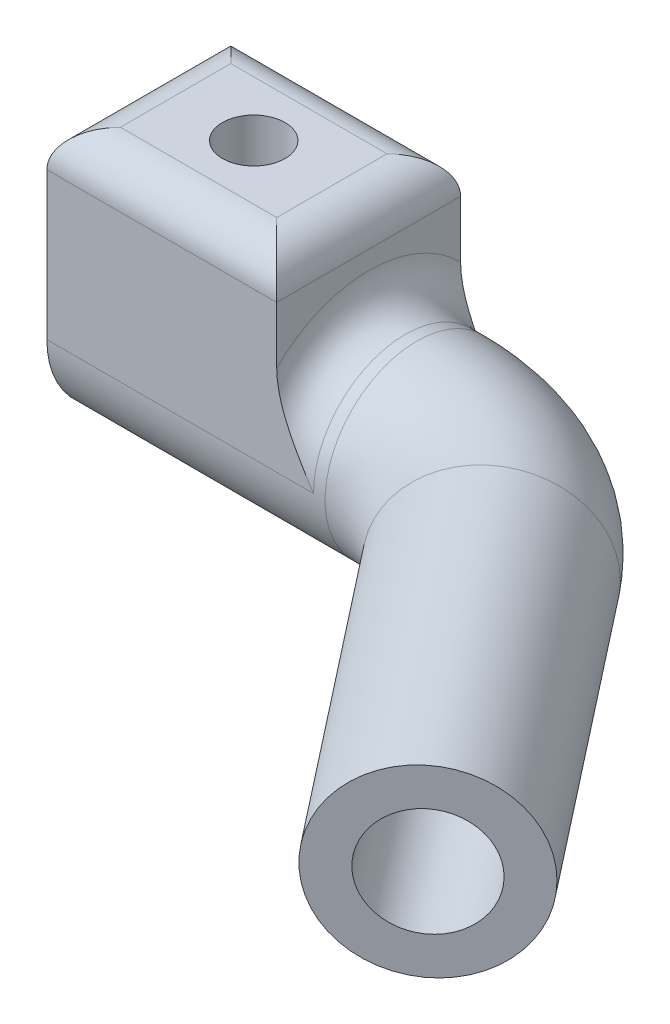
SolidWorks part; units mm, degrees
ref_plane "Front" through (0, 0, 0) normal (0, 0, 1) x (1, 0, 0)
ref_plane "Top" through (0, 0, 0) normal (0, 1, 0) x (1, 0, 0)
ref_plane "Right" through (0, 0, 0) normal (1, 0, 0) x (0, 0, -1)
sketch "Sketch1" plane through (0, 0, 0) normal (0, 1, 0) x (1, 0, 0)
  line L0 (0, 0) -> (15.1284, 0)
  line L1 (23.0028, -3.8361) -> (35.4097, -19.6861)
  line L2 (15.1284, 0) -> (20, 0) construction
  line L3 (23.0028, -3.8361) -> (20, 0) construction
  arc A0 (23.0028, -3.8361) -> (15.1284, 0) centre (15.1284, -10) ccw
  point P10 (20, 0)
  dimension "D1" = 10
  dimension "D2" = 128.053
  dimension "D3" = 20
  dimension "D4" = 25
sketch "Sketch2" plane through (0, 0, 0) normal (1, 0, 0) x (0, 0, -1)
  circle A1 centre (0, 0) radius 5
  dimension "D1" = 10
sweep "Sweep1" add profiles "Sketch2" path "Sketch1"
sketch "Sketch3" plane through (0, 0, 0) normal (0, 1, 0) x (1, 0, 0)
  line L1 (0, 0) -> (6.25, 0) construction
  line L2 (0, -5) -> (15.1284, -5) construction
  line L3 (12.5, 5) -> (0, 5)
  line L4 (12.5, 5) -> (12.5, -5)
  line L5 (12.5, -5) -> (0, -5)
  line L6 (0, 5) -> (0, -5)
  line L7 (12.5, 5) -> (0, -5) construction
  line L8 (12.5, -5) -> (0, 5) construction
  line L9 (0, 5) -> (0, -5) construction
  dimension "D1" = 12.5
extrude "Boss-Extrude1" add sketch "Sketch3" along normal blind 10
sketch "Sketch4" plane through (0, 0, 0) normal (-1, 0, 0) x (0, 0, 1)
  line L0 (-2.6268, 1.55) -> (2.6268, 1.55)
  circle A0 centre (0, 0) radius 3.05 construction
  arc A1 (-2.6268, 1.55) -> (2.6268, 1.55) centre (0, 0) ccw
  point P5 (0, -3.05)
  dimension "D1" = 6.1
  dimension "D2" = 4.6
extrude "Cut-Extrude1" cut sketch "Sketch4" against normal blind 12.5
sketch "Sketch5" plane through (23.0084, 0, 29.3935) normal (0.6164, 0, 0.7874) x (0.7874, 0, -0.6164)
  line L0 (3.0819, 10) -> (-3.0819, 10) construction
  circle A0 centre (15.7489, 0) radius 2.95
  dimension "D1" = 5.9
sketch "Sketch6" plane through (0, 10, 0) normal (0, 1, 0) x (1, 0, 0)
  line L0 (0, 5) -> (12.5, -5) construction
  line L1 (0, -5) -> (12.5, 5) construction
  circle A0 centre (6.25, 0) radius 1.7
  point P8 (6.25, 0)
  dimension "D1" = 3.4
extrude "Cut-Extrude2" cut sketch "Sketch6" against normal up to next
extrude "Cut-Extrude3" cut sketch "Sketch5" against normal blind 10
fillet "Fillet1" radius 2 5 edges at (12.5, 5, 0) (0, 10, 0) (6.25, 10, -5) (12.5, 10, 0) (6.25, 10, 5)
